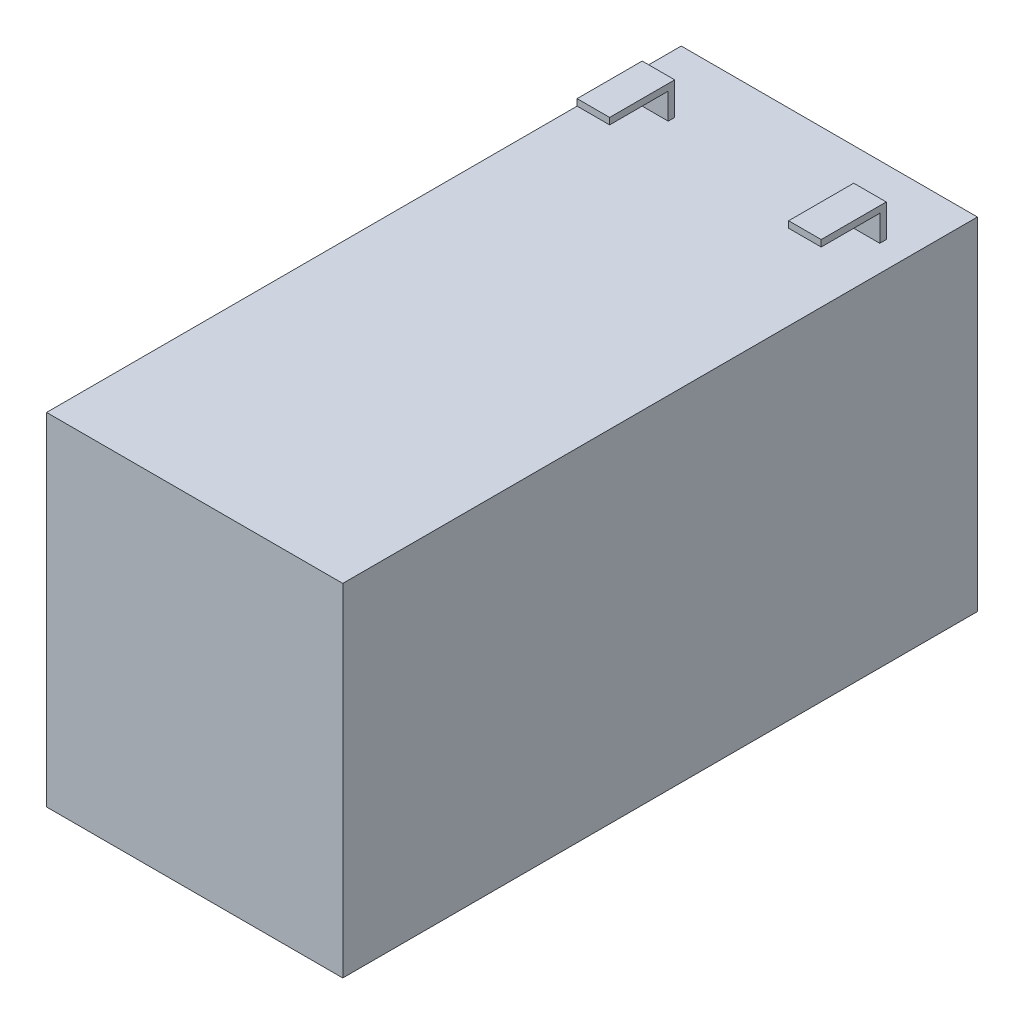
SolidWorks part; units mm, degrees
ref_plane "前视基准面" through (0, 0, 0) normal (0, 0, 1) x (1, 0, 0)
ref_plane "上视基准面" through (0, 0, 0) normal (0, 1, 0) x (1, 0, 0)
ref_plane "右视基准面" through (0, 0, 0) normal (1, 0, 0) x (0, 0, -1)
sketch "草图1" plane through (0, 0, 0) normal (0, 1, 0) x (1, 0, 0)
  line L1 (0, 0) -> (45.5, 0)
  line L2 (0, 0) -> (0, 97.5)
  line L3 (0, 97.5) -> (45.5, 97.5)
  line L4 (45.5, 0) -> (45.5, 97.5)
  dimension "D1" = 97.5
  dimension "D2" = 45.5
extrude "拉伸1" add sketch "草图1" along normal blind 52.5
sketch "草图3" plane through (0, 52.5, 0) normal (0, 1, 0) x (-1, 0, 0)
  line L0 (-45.5, -97.5) -> (0, -97.5) construction
  line L1 (-4, -87.5) -> (-9, -87.5)
  line L2 (-4, -87.5) -> (-4, -86.5)
  line L3 (-4, -86.5) -> (-9, -86.5)
  line L4 (-9, -87.5) -> (-9, -86.5)
  line L5 (0, -97.5) -> (0, 0) construction
  dimension "D1" = 10
  dimension "D2" = 4
  dimension "D3" = 5
  dimension "D4" = 1
ref_plane "基准面1" through (4, 0, 0) normal (-1, 0, 0) x (0, 0, 1)
sketch "草图4" plane through (4, 0, 0) normal (-1, 0, 0) x (0, 0, 1)
  line L0 (-87.5, 52.5) -> (-87.5, 57.5)
  line L1 (-87.5, 57.5) -> (-77.5, 57.5)
  dimension "D1" = 10
  dimension "D2" = 5
sweep "扫描1" add profiles "草图3" path "草图4"
ref_plane "基准面2" through (22.75, 0, 0) normal (-1, 0, 0) x (0, 0, 1)
mirror "镜向2" about plane through (22.75, 0, 0) normal (-1, 0, 0) of "扫描1"
